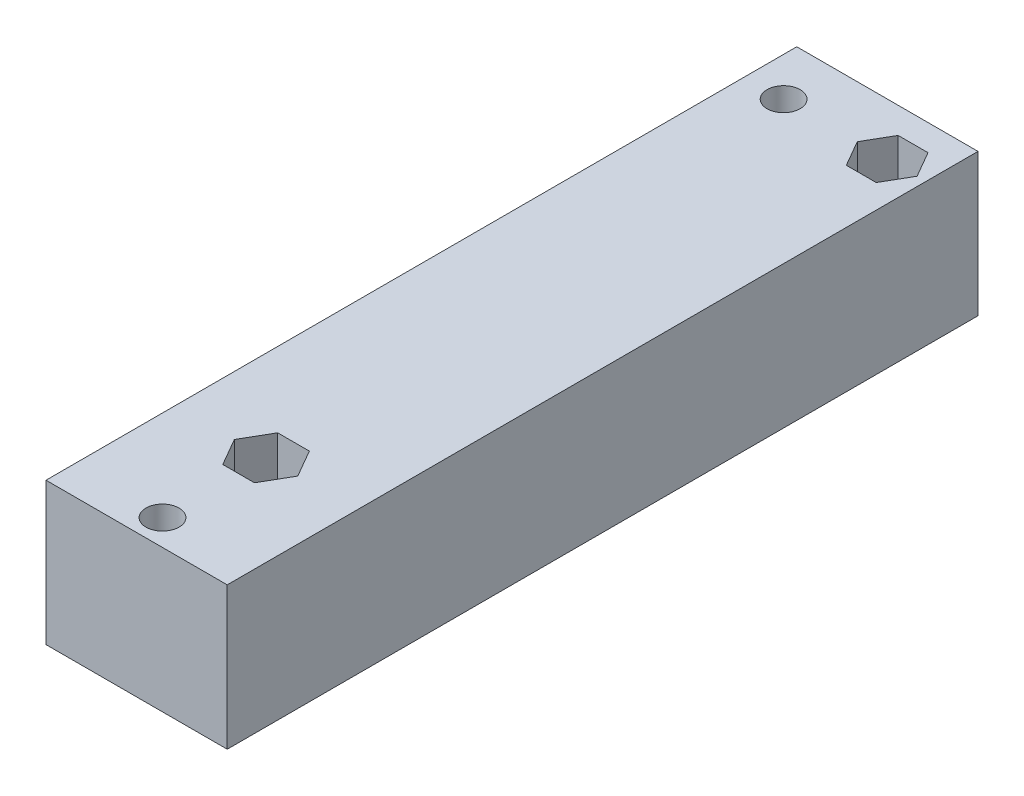
SolidWorks part; units mm, degrees
ref_plane "Front Plane" through (0, 0, 0) normal (0, 0, 1) x (1, 0, 0)
ref_plane "Top Plane" through (0, 0, 0) normal (0, 1, 0) x (1, 0, 0)
ref_plane "Right Plane" through (0, 0, 0) normal (1, 0, 0) x (0, 0, -1)
sketch "Sketch1" plane through (0, 0, 0) normal (0, 0, 1) x (1, 0, 0)
  line L1 (0, 0) -> (22.225, 0)
  line L2 (0, 0) -> (0, 17.4625)
  line L3 (0, 17.4625) -> (22.225, 17.4625)
  line L4 (22.225, 0) -> (22.225, 17.4625)
  dimension "D1" = 17.4625
  dimension "D2" = 22.225
extrude "Boss-Extrude1" add sketch "Sketch1" along normal blind 92.075
sketch "Sketch2" plane through (0, 0, 0) normal (0, -1, 0) x (1, 0, 0)
  line L0 (0, 92.075) -> (0, 0) construction
  line L1 (14.9986, 76.2) -> (13.0556, 79.5655)
  line L2 (13.0556, 79.5655) -> (9.1694, 79.5655)
  line L3 (9.1694, 79.5655) -> (7.2264, 76.2)
  line L4 (7.2264, 76.2) -> (9.1694, 72.8345)
  line L5 (9.1694, 72.8345) -> (13.0556, 72.8345)
  line L6 (13.0556, 72.8345) -> (14.9986, 76.2)
  line L7 (0, 92.075) -> (22.225, 92.075) construction
  line L9 (6.5956, 9.5517) -> (2.9294, 9.5517)
  line L10 (2.9294, 9.5517) -> (1.0963, 6.3767)
  line L11 (1.0963, 6.3767) -> (2.9294, 3.2017)
  line L12 (2.9294, 3.2017) -> (6.5956, 3.2017)
  line L13 (6.5956, 3.2017) -> (8.4287, 6.3767)
  line L14 (8.4287, 6.3767) -> (6.5956, 9.5517)
  circle A0 centre (11.1125, 76.2) radius 3.3655 construction
  circle A7 centre (4.7625, 6.3767) radius 3.175 construction
  circle A8 centre (17.4625, 6.3767) radius 2.032
  circle A9 centre (11.1125, 88.9) radius 2.032
  point P1 (0, 46.0375)
  point P13 (11.1125, 92.075)
  dimension "D2" = 4.064
  dimension "D7" = 12.7
  dimension "D1" = 6.731
  dimension "D3" = 12.7
  dimension "D4" = 15.875
  dimension "D6" = 6.35
extrude "Cut-Extrude1" cut sketch "Sketch2" against normal up to next
ref_plane "Plane1" through (-2.54, 0, 0) normal (-1, 0, 0) x (0, 0, 1)
mirror "Mirror3" about plane through (-2.54, 0, 0) normal (-1, 0, 0) of bodies 102
sketch "Sketch3" plane through (0, 0, 92.075) normal (0, 0, 1) x (1, 0, 0)
  line L0 (0, 17.4625) -> (0, 0) construction
  line L6 (0, 17.4625) -> (22.225, 17.4625)
  line L7 (0, 17.4625) -> (0, 0)
  line L8 (0, 0) -> (22.225, 0)
  line L9 (22.225, 17.4625) -> (22.225, 0)
extrude "Cut-Extrude2" cut sketch "Sketch3" against normal up to surface (92.075 mm away) up to face at (11.1125, 8.7312, 0)
